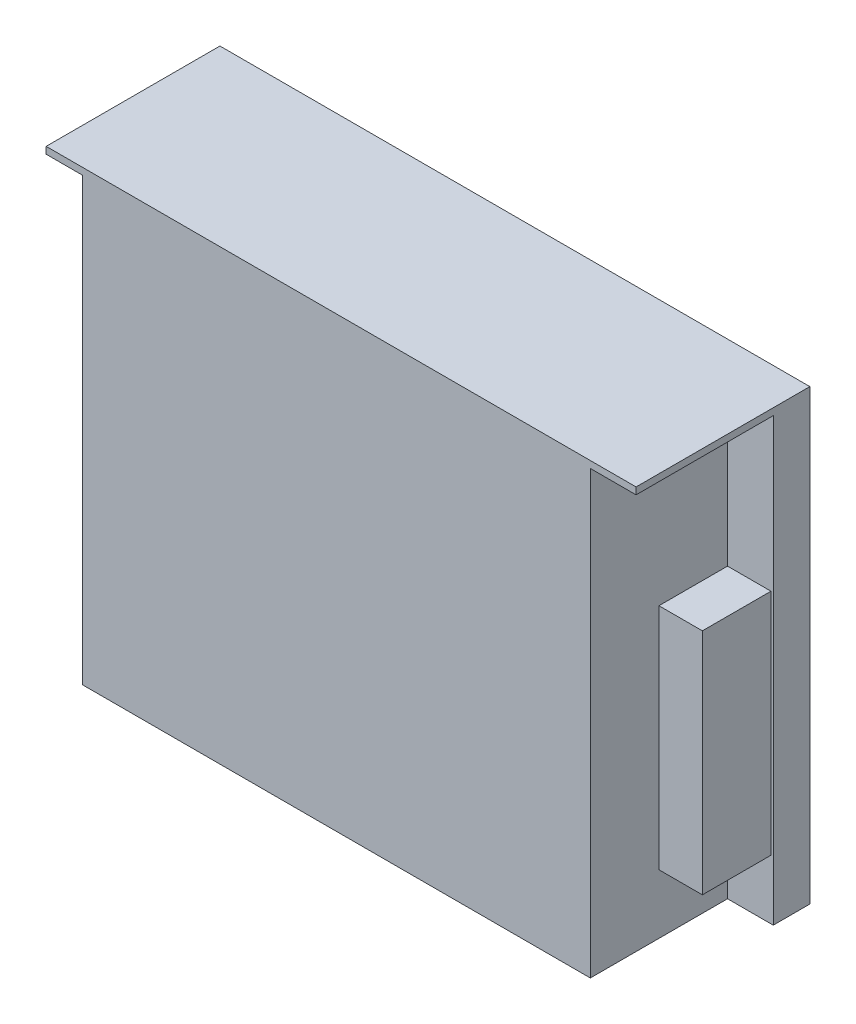
SolidWorks part; units mm, degrees
material "镀铬不锈钢"
ref_plane "前视基准面" through (0, 0, 0) normal (0, 0, 1) x (1, 0, 0)
ref_plane "上视基准面" through (0, 0, 0) normal (0, 1, 0) x (1, 0, 0)
ref_plane "右视基准面" through (0, 0, 0) normal (1, 0, 0) x (0, 0, -1)
sketch "草图1" plane through (0, 0, 0) normal (0, 0, 1) x (1, 0, 0)
  line L1 (0, 0) -> (129, 0)
  line L2 (0, 0) -> (0, 98)
  line L3 (0, 98) -> (129, 98)
  line L4 (129, 0) -> (129, 98)
  dimension "D1" = 98
  dimension "D2" = 129
extrude "凸台-拉伸1" add sketch "草图1" along normal blind 38
sketch "草图2" plane through (0, 0, 38) normal (0, 0, 1) x (1, 0, 0)
  line L0 (129, 98) -> (0, 98) construction
  line L1 (129, 0) -> (119, 0)
  line L2 (129, 0) -> (129, 96.5)
  line L3 (129, 96.5) -> (119, 96.5)
  line L4 (119, 0) -> (119, 96.5)
  dimension "D1" = 1.5
  dimension "D2" = 10
extrude "切除-拉伸1" cut sketch "草图2" against normal blind 30
sketch "草图3" plane through (0, 0, 8) normal (0, 0, 1) x (1, 0, 0)
  line L1 (128.5, 13) -> (119, 13)
  line L2 (128.5, 13) -> (128.5, 63)
  line L3 (128.5, 63) -> (119, 63)
  line L4 (119, 13) -> (119, 63)
  line L5 (119, 96.5) -> (119, 0) construction
  line L6 (119, 0) -> (129, 0) construction
  dimension "D1" = 13
  dimension "D2" = 50
  dimension "D3" = 9.5
extrude "凸台-拉伸2" add sketch "草图3" along normal blind 15
sketch "草图4" plane through (0, 0, 0) normal (-1, 0, 0) x (0, 0, 1)
  line L1 (38, 0) -> (9, 0)
  line L2 (38, 0) -> (38, 96.5)
  line L3 (38, 96.5) -> (9, 96.5)
  line L4 (9, 0) -> (9, 96.5)
  line L5 (38, 98) -> (0, 98) construction
  dimension "D1" = 29
  dimension "D2" = 1.5
extrude "切除-拉伸2" cut sketch "草图4" against normal blind 8
chamfer "倒角1" distance 8 angle 45 1 edges at (8, 48.25, 9)
sketch "草图5" plane through (0, 0, 0) normal (0, -1, 0) x (1, 0, 0)
  line L0 (0, 9) -> (8, 17)
  line L1 (8, 17) -> (8, 1.5)
  line L3 (8, 1.5) -> (0, 1.5)
  line L4 (0, 1.5) -> (0, 9)
  line L5 (0, 0) -> (129, 0) construction
  dimension "D1" = 1.5
extrude "切除-拉伸3" cut sketch "草图5" against normal blind 10
